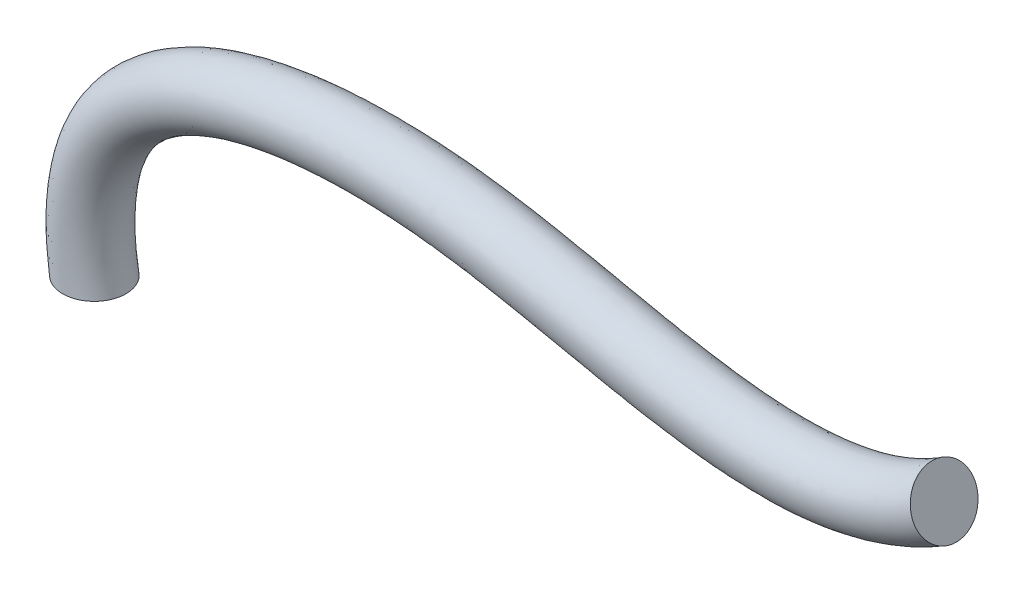
SolidWorks part; units mm, degrees
material "60A Urethane Rubber, Black"
ref_plane "Front Plane" through (0, 0, 0) normal (0, 0, 1) x (1, 0, 0)
ref_plane "Top Plane" through (0, 0, 0) normal (0, 1, 0) x (1, 0, 0)
ref_plane "Right Plane" through (0, 0, 0) normal (1, 0, 0) x (0, 0, -1)
sketch "Sketch1" plane through (0, 0, 0) normal (0, 1, 0) x (1, 0, 0)
  circle A0 centre (0, 0) radius 3.05
  dimension "D1" = 6.1
sketch "Sketch2" plane through (0, 0, 0) normal (0, 0, 1) x (1, 0, 0)
  line L0 (3.05, 0) -> (-3.05, 0) construction
  spline S0 degree 3 poles (0, 0) (-3.2594, 20.3421) (19.8512, 25.1986) (51.8906, 20.6398) (69.2026, 14.3358) (81.8249, 22.0759) knots 0 0 0 0 0.452591 0.545591 1 1 1 1
  point P2 (22.0457, 66.1278)
  point P4 (111.4333, 25.9801)
  point P5 (50.149, 13.9358)
  point P6 (45.3077, 25.6259)
  point P8 (35.4315, 22.9333)
  point P9 (81.8249, 22.0759)
sweep "Sweep1" add profiles "Sketch1" path "Sketch2"
